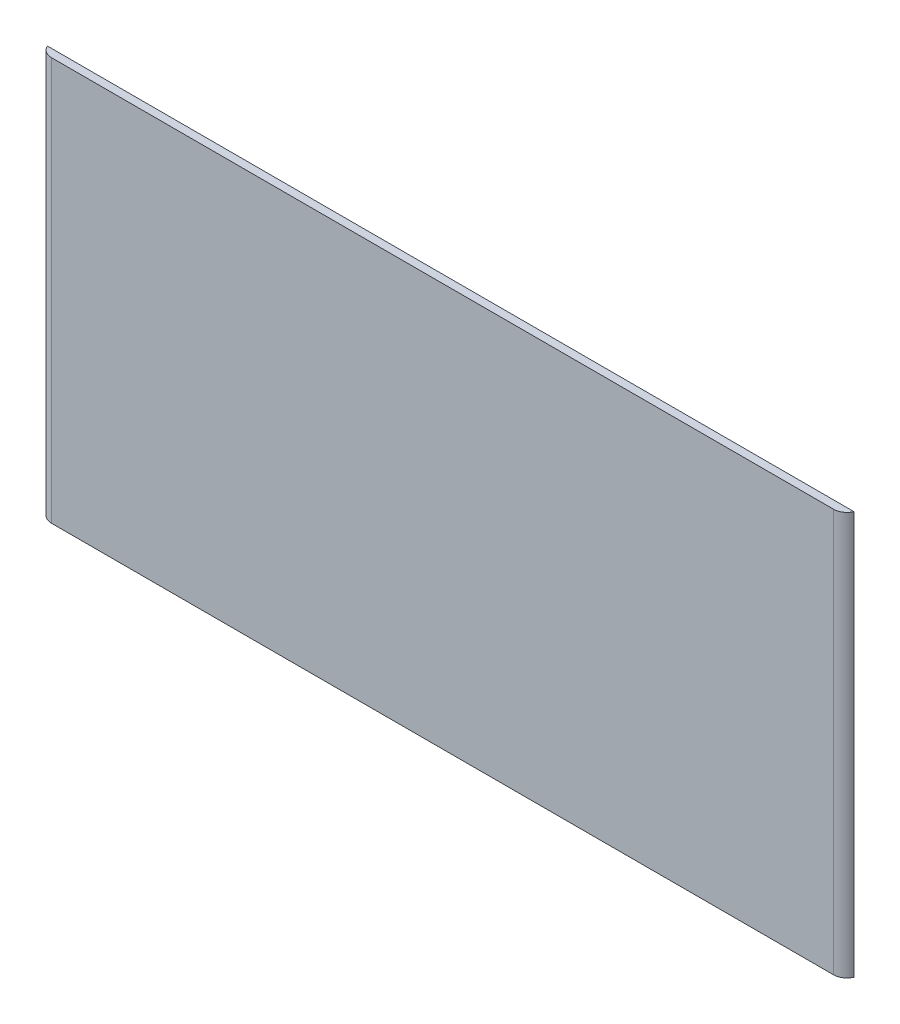
SolidWorks part; units mm, degrees
ref_plane "Plano frontal" through (0, 0, 0) normal (0, 0, 1) x (1, 0, 0)
ref_plane "Plano superior" through (0, 0, 0) normal (0, 1, 0) x (1, 0, 0)
ref_plane "Plano direito" through (0, 0, 0) normal (1, 0, 0) x (0, 0, -1)
sketch "Esboço1" plane through (0, 0, 0) normal (0, 0, 1) x (1, 0, 0)
  line L1 (0, 0) -> (600, 0)
  line L2 (0, 0) -> (0, -300)
  line L3 (0, -300) -> (600, -300)
  line L4 (600, 0) -> (600, -300)
  dimension "D1" = 600
  dimension "D2" = 300
extrude "Ressalto-extrusão2" add sketch "Esboço1" along normal blind 6
fillet "Filete1" radius 10 1 edges at (600, -150, 6)
fillet "Filete2" radius 10 1 edges at (0, -150, 6)
sketch "Esboço2" plane through (0, 0, 6) normal (0, 0, 1) x (1, 0, 0)
  line L5 (294.7913, -142.5) -> (309.7913, -142.5)
  line L6 (294.7913, -142.5) -> (294.7913, -157.5)
  line L7 (294.7913, -157.5) -> (309.7913, -157.5)
  line L8 (309.7913, -142.5) -> (309.7913, -157.5)
  line L9 (294.7913, -142.5) -> (309.7913, -157.5) construction
  line L10 (294.7913, -157.5) -> (309.7913, -142.5) construction
  point P9 (302.2913, -150)
